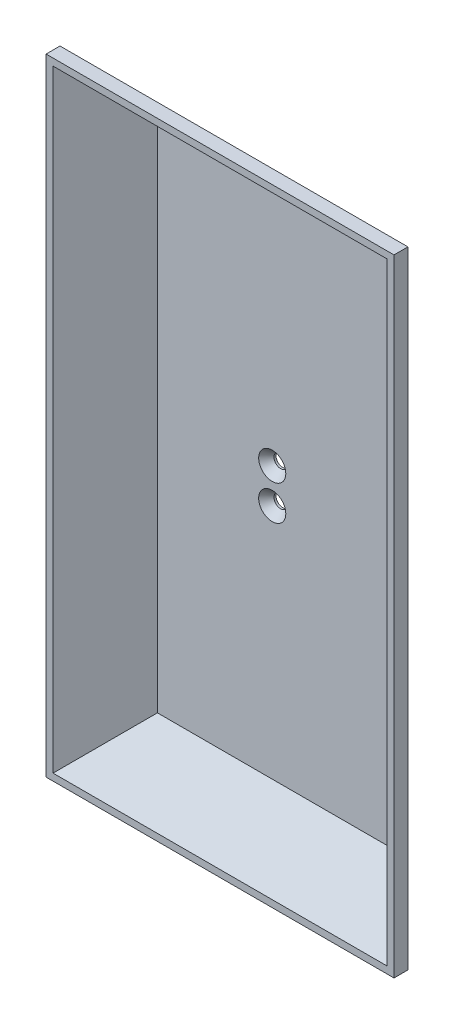
SolidWorks part; units mm, degrees
ref_plane "정면" through (0, 0, 0) normal (0, 0, 1) x (1, 0, 0)
ref_plane "윗면" through (0, 0, 0) normal (0, 1, 0) x (1, 0, 0)
ref_plane "우측면" through (0, 0, 0) normal (1, 0, 0) x (0, 0, -1)
sketch "스케치1" plane through (0, 0, 0) normal (0, 0, 1) x (1, 0, 0)
  line L1 (-50, 90) -> (50, 90)
  line L2 (-50, 90) -> (-50, -90)
  line L3 (-50, -90) -> (50, -90)
  line L4 (50, 90) -> (50, -90)
  line L5 (-50, 90) -> (50, -90) construction
  line L6 (-50, -90) -> (50, 90) construction
  point P0 (0, 0)
  dimension "D1" = 100
  dimension "D2" = 180
extrude "보스-돌출1" add sketch "스케치1" along normal blind 4
sketch "스케치2" plane through (0, 0, 0) normal (0, 0, 1) x (1, 0, 0)
  line L1 (-6, 11) -> (6, 11)
  line L2 (-6, 11) -> (-6, -11)
  line L3 (-6, -11) -> (6, -11)
  line L4 (6, 11) -> (6, -11)
  line L5 (-6, 11) -> (6, -11) construction
  line L6 (-6, -11) -> (6, 11) construction
  point P0 (0, 0)
  dimension "D1" = 12
  dimension "D2" = 22
extrude "보스-돌출2" [suppressed] add sketch "스케치2" against normal blind 5
sketch "스케치3" [suppressed] plane through (0, 0, -5) normal (0, 0, -1) x (-1, 0, 0)
  line L0 (0, 0) -> (6, 0) construction
  line L1 (6, 11) -> (6, -11) construction
  line L2 (0, 5) -> (0, 0) construction
  circle A0 centre (0, 5) radius 1.9
  circle A1 centre (0, -5) radius 1.9
  dimension "D1" = 3.8
  dimension "D2" = 10
extrude "컷-돌출1" [suppressed] cut sketch "스케치3" against normal through all
sketch "스케치4" plane through (0, 0, 4) normal (0, 0, 1) x (1, 0, 0)
  line L1 (-50, 90) -> (50, 90)
  line L2 (-50, 90) -> (-50, -90)
  line L3 (-50, -90) -> (50, -90)
  line L4 (50, 90) -> (50, -90)
  line L5 (-50, 90) -> (50, -90) construction
  line L6 (-50, -90) -> (50, 90) construction
  line L7 (-48, 88) -> (48, 88)
  line L8 (-48, 88) -> (-48, -88)
  line L9 (-48, -88) -> (48, -88)
  line L10 (48, 88) -> (48, -88)
  line L11 (-48, 88) -> (48, -88) construction
  line L12 (-48, -88) -> (48, 88) construction
  point P0 (0, 0)
  point P7 (0, 0)
  point P12 (41.7052, -75.0694)
  point P13 (46.5385, -83.7693)
  point P14 (39.001, -70.2018)
  point P15 (47.1554, -80.0647)
  dimension "D1" = 2
  dimension "D2" = 2
extrude "보스-돌출3" add sketch "스케치4" along normal blind 15
chamfer "모따기1" distance 15 angle 45 8 edges at (-48, 0, 4) (0, -88, 4) (50, 0, 0) (0, 90, 0) (-50, 0, 0) (0, -90, 0) (48, 0, 4) (0, 88, 4)
sketch "스케치6" plane through (0, 0, 0) normal (0, 0, 1) x (1, 0, 0)
  line L0 (0, 0) -> (-5, 0) construction
  line L1 (0, 5) -> (0, 0) construction
  circle A0 centre (0, 5) radius 1.9
  circle A1 centre (0, -5) radius 1.9
  dimension "D2" = 3.8
  dimension "D1" = 5
  dimension "D3" = 10
extrude "컷-돌출3" cut sketch "스케치6" along normal blind 10 and the other way through all
chamfer "모따기2" distance 2 distance2 2.4 2 edges at (1.9, 5, 4) (1.9, -5, 4) first distance on face at (1.9, 5, 4)
sketch "스케치10" plane through (0, 0, 0) normal (0, 0, -1) x (-1, 0, 0)
  line L1 (-6.1, 11.15) -> (6.1, 11.15)
  line L2 (-6.1, 11.15) -> (-6.1, -11.15)
  line L3 (-6.1, -11.15) -> (6.1, -11.15)
  line L4 (6.1, 11.15) -> (6.1, -11.15)
  line L5 (-6.1, 11.15) -> (6.1, -11.15) construction
  line L6 (-6.1, -11.15) -> (6.1, 11.15) construction
  point P0 (0, 0)
  dimension "D1" = 12.2
  dimension "D2" = 22.3
extrude "컷-돌출4" cut sketch "스케치10" against normal blind 1
